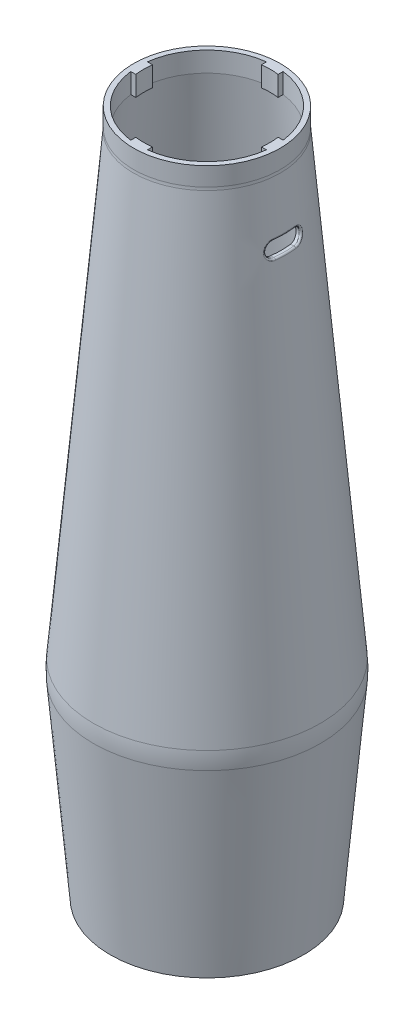
SolidWorks part; units mm, degrees
material "PVC Rígido"
ref_plane "Alzado" through (0, 0, 0) normal (0, 0, 1) x (1, 0, 0)
ref_plane "Planta" through (0, 0, 0) normal (0, 1, 0) x (1, 0, 0)
ref_plane "Vista lateral" through (0, 0, 0) normal (1, 0, 0) x (0, 0, -1)
sketch "Croquis1" plane through (0, 0, 0) normal (0, 1, 0) x (1, 0, 0)
  line L0 (0, -20.5) -> (0, 20.5) construction
  line L1 (20.5, 0) -> (-20.5, 0) construction
  line L2 (2.5, -20.347) -> (2.5, -18.8348)
  line L4 (-2.5, 20.347) -> (-2.5, 18.8348)
  line L6 (2.5, 20.347) -> (2.5, 18.8348)
  line L8 (-2.5, -20.347) -> (-2.5, -18.8348)
  line L10 (20.347, -2.5) -> (18.8348, -2.5)
  line L11 (-20.347, 2.5) -> (-18.8348, 2.5)
  line L13 (-20.347, -2.5) -> (-18.8348, -2.5)
  line L16 (20.347, 2.5) -> (18.8348, 2.5)
  arc A0 (-18.8348, 2.5) -> (-18.8348, -2.5) centre (0, 0) ccw
  arc A1 (20.347, 2.5) -> (2.5, 20.347) centre (0, 0) ccw
  arc A2 (2.5, 18.8348) -> (-2.5, 18.8348) centre (0, 0) ccw
  arc A3 (18.8348, -2.5) -> (18.8348, 2.5) centre (0, 0) ccw
  arc A4 (-2.5, -18.8348) -> (2.5, -18.8348) centre (0, 0) ccw
  circle A5 centre (0, 0) radius 22
  arc A6 (2.5, -20.347) -> (20.347, -2.5) centre (0, 0) ccw
  arc A7 (-20.347, -2.5) -> (-2.5, -20.347) centre (0, 0) ccw
  arc A8 (-2.5, 20.347) -> (-20.347, 2.5) centre (0, 0) ccw
  dimension "D1" = 38
  dimension "D2" = 41
  dimension "D4" = 44
  dimension "D3" = 1.5122
extrude "Saliente-Extruir1" add sketch "Croquis1" against normal blind 6
sketch "Croquis3" plane through (0, 0, 0) normal (0, 0, 1) x (1, 0, 0)
  line L0 (-22, 0) -> (-34.2484, 140)
  line L2 (-32.7484, 140) -> (-20.5, 0)
  line L3 (0, 0) -> (0, 120) construction
  line L4 (22, 0) -> (-22, 0) construction
  line L6 (-22, 0) -> (-20.5, 0)
  line L7 (-34.2484, 140) -> (-28.9991, 200)
  line L8 (-28.9991, 200) -> (-27.4991, 200)
  line L9 (-27.4991, 200) -> (-32.7484, 140)
  dimension "D1" = 140
  dimension "D2" = 95
  dimension "D3" = 1.5
  dimension "D4" = 1.5
  dimension "D6" = 1.5
  dimension "D7" = 60
  dimension "D8" = 170
revolve "Revolución1" add sketch "Croquis3" angle 360 about L3
fillet "Redondeo1" radius 30 1 edges at (0, 140, -34.2484)
fillet "Redondeo2" radius 10 1 edges at (0, 0, 22)
ref_plane "Plano2" through (21.8329, -1.9101, 0) normal (0.9962, -0.0872, 0) x (0, 0, -1)
sketch "Croquis5" plane through (21.8329, -1.9101, 0) normal (0.9962, -0.0872, 0) x (0, 0, -1)
  line L0 (-3, 20) -> (3, 20) construction
  line L1 (-3, 22.25) -> (3, 22.25)
  line L2 (-3, 17.75) -> (3, 17.75)
  arc A0 (-3, 22.25) -> (-3, 17.75) centre (-3, 20) ccw
  arc A1 (3, 17.75) -> (3, 22.25) centre (3, 20) ccw
  point P2 (0, 20)
  dimension "D2" = 6
  dimension "D1" = 4.5
  dimension "D3" = 20
extrude "Cortar-Extruir1" cut sketch "Croquis5" against normal blind 20
fillet "Redondeo3" radius 0.5 4 edges at (23.3799, 15.7723, 0) (23.0179, 18.3461, 5.2322) (23.7721, 20.2552, 0) (22.9674, 17.7827, -5.2321)
sketch "Croquis9" plane through (0, 0, 0) normal (0, 0, 1) x (1, 0, 0)
  line L0 (0, 0) -> (0, -6) construction
  line L1 (-2.5, -6) -> (2.5, -6) construction
  line L2 (-22.6872, 25) -> (-17.6872, 25)
  line L3 (-32.7484, 140) -> (-20.5, 0) construction
  line L4 (-17.6872, 25) -> (-17.6872, 30)
  line L5 (-17.6872, 30) -> (-23.1247, 30)
  line L6 (-23.1247, 30) -> (-22.6872, 25)
  line L7 (-26.9742, 74) -> (-17.6872, 74)
  line L8 (-17.6872, 74) -> (-17.6872, 79)
  line L9 (-17.6872, 79) -> (-27.4116, 79)
  line L10 (-27.4116, 79) -> (-26.9742, 74)
  line L11 (-2.5, 0) -> (-20.347, 0) construction
  line L12 (-27.4991, 200) -> (-27.4991, -42.2824) construction
  line L14 (0, 0) -> (0, 101.7704) construction
  line L15 (0, 0) -> (0, 120) construction
  line L16 (17.6872, 30) -> (23.1247, 30)
  line L17 (17.6872, 25) -> (17.6872, 30)
  line L18 (22.6872, 25) -> (17.6872, 25)
  line L19 (23.1247, 30) -> (22.6872, 25)
  line L20 (17.6872, 79) -> (27.4116, 79)
  line L21 (17.6872, 74) -> (17.6872, 79)
  line L22 (26.9742, 74) -> (17.6872, 74)
  line L23 (27.4116, 79) -> (26.9742, 74)
  dimension "D1" = 5
  dimension "D2" = 25
  dimension "D3" = 54
extrude "Saliente-Extruir2" add sketch "Croquis9" along normal mid plane 5
sketch "Croquis11" plane through (0, 0, 0) normal (0, 0, 1) x (1, 0, 0)
  line L0 (-17.6872, 25) -> (-17.6872, 30) construction
  line L1 (-17.6872, 26) -> (-21.6872, 26)
  line L2 (-17.6872, 26) -> (-17.6872, 30)
  line L3 (-17.6872, 30) -> (-21.6872, 30)
  line L4 (-21.6872, 26) -> (-21.6872, 30)
  line L5 (-17.6872, 30) -> (-22.9891, 30) construction
  line L6 (0, 0) -> (0, 81.6267) construction
  line L11 (0, 0) -> (0, 120) construction
  line L12 (17.6872, 30) -> (21.6872, 30)
  line L13 (-17.6872, 74) -> (-21.6872, 74)
  line L14 (-17.6872, 74) -> (-17.6872, 79)
  line L15 (-17.6872, 79) -> (-21.6872, 79)
  line L16 (-21.6872, 74) -> (-21.6872, 79)
  line L17 (21.6872, 26) -> (21.6872, 30)
  line L18 (17.6872, 26) -> (21.6872, 26)
  line L19 (17.6872, 26) -> (17.6872, 30)
  line L20 (17.6872, 79) -> (21.6872, 79)
  line L21 (21.6872, 74) -> (21.6872, 79)
  line L22 (17.6872, 74) -> (21.6872, 74)
  line L23 (17.6872, 74) -> (17.6872, 79)
  dimension "D1" = 4
  dimension "D2" = 4
  dimension "D3" = 5
extrude "Cortar-Extruir2" cut sketch "Croquis11" against normal mid plane 2.5
move or copy body "Sólido-Mover/Copiar1" bodies to move or copy 106 copy no rotation origin (0, 97, 0) rotation axis (1, 0, 0) rotation angle 180
sketch "Croquis12" plane through (0, -6, 0) normal (0, -1, 0) x (1, 0, 0)
  line L0 (0, 14) -> (0, -14) construction
  line L1 (-22, 14) -> (22, 14)
  line L2 (-22, 14) -> (-22, -14)
  line L3 (-22, -14) -> (22, -14)
  line L4 (22, 14) -> (22, -14)
  line L5 (-22, 0) -> (22, 0) construction
  point P10 (0, 0)
  dimension "D1" = 44
  dimension "D2" = 28
